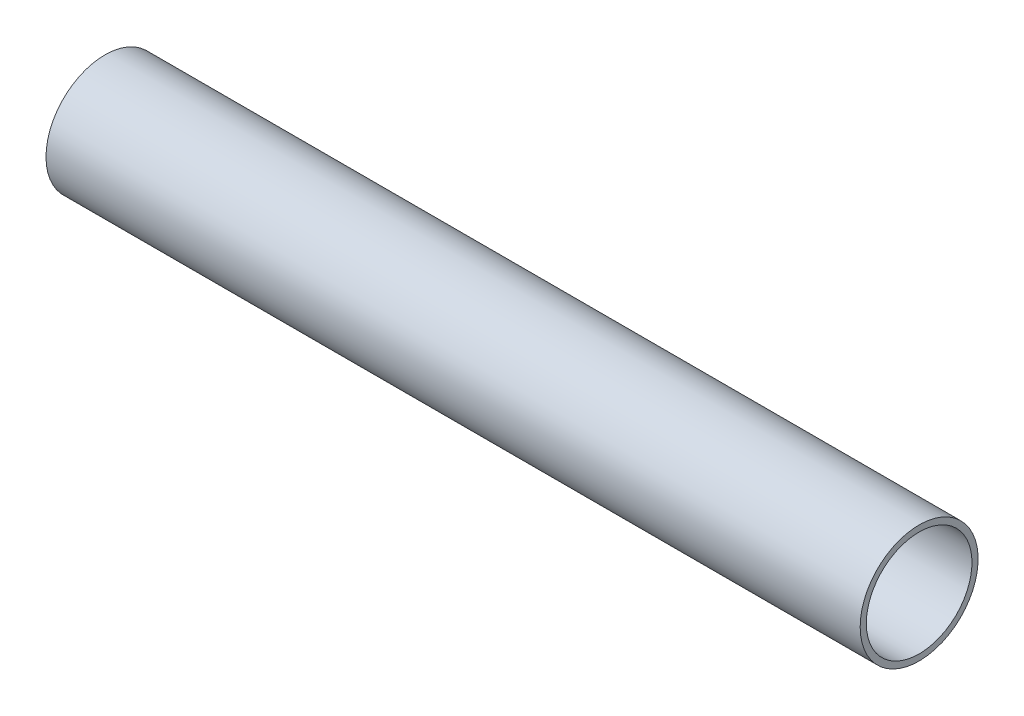
SolidWorks part; units mm, degrees
ref_plane "Front Plane" through (0, 0, 0) normal (0, 0, 1) x (1, 0, 0)
ref_plane "Top Plane" through (0, 0, 0) normal (0, 1, 0) x (1, 0, 0)
ref_plane "Right Plane" through (0, 0, 0) normal (1, 0, 0) x (0, 0, -1)
sketch "Leg_Piston Sketch" plane through (0, 0, 0) normal (0, 0, 1) x (1, 0, 0)
  line L0 (-3000, 0) -> (3000, 0) construction
  line L1 (1240, 0) -> (1240, 13.4)
  line L2 (1240, 13.4) -> (1425, 13.4)
  line L3 (1425, 13.4) -> (1425, 12)
  line L4 (1425, 12) -> (1242, 12)
  line L5 (1242, 12) -> (1242, 0)
  line L6 (1242, 0) -> (1240, 0)
revolve "Leg_Piston" add sketch "Leg_Piston Sketch" angle 360 about L0
ref_axis "Engine Axis" through (1434.25, 0, 0) along (-1, 0, 0)
